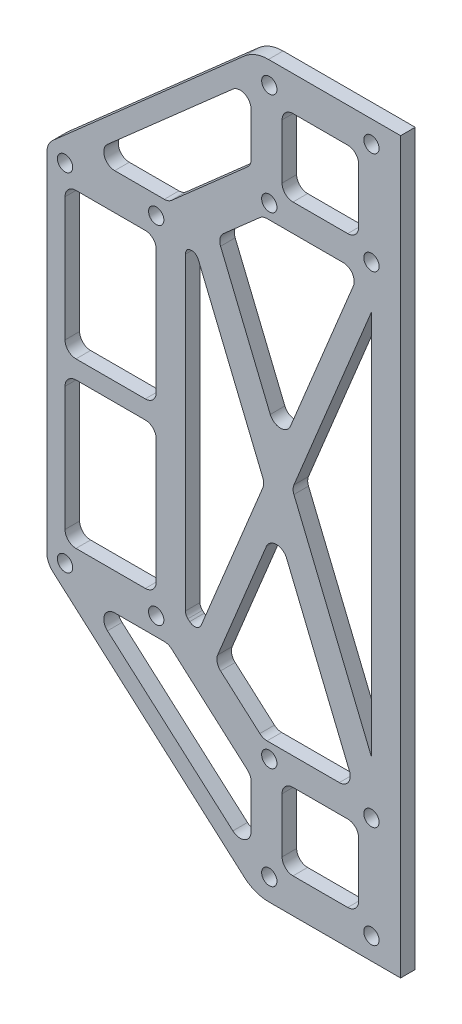
SolidWorks part; units mm, degrees
material "Thornel Mat VMA"
ref_plane "前视基准面" through (0, 0, 0) normal (0, 0, 1) x (1, 0, 0)
ref_plane "上视基准面" through (0, 0, 0) normal (0, 1, 0) x (1, 0, 0)
ref_plane "右视基准面" through (0, 0, 0) normal (1, 0, 0) x (0, 0, -1)
other "Configuration Table"
sketch "草图1" plane through (0, 0, 0) normal (0, 0, 1) x (1, 0, 0)
  line L0 (-20, 100) -> (-77, 55)
  line L1 (-20, -100) -> (20, -100)
  line L2 (-20, -100) -> (-20, 100)
  line L3 (-20, 100) -> (20, 100)
  line L4 (20, -100) -> (20, 100)
  line L5 (-20, -100) -> (20, 100) construction
  line L6 (-20, 100) -> (20, -100) construction
  line L7 (-77, 55) -> (-77, -55)
  line L8 (-77, -55) -> (-20, -100)
  line L9 (0, 0) -> (50000, 0) construction
  line L10 (0, 100) -> (0, -100) construction
  line L11 (-72, -47.5) -> (-47, -47.5) construction
  line L12 (-72, -47.5) -> (-72, 47.5) construction
  line L13 (-72, 47.5) -> (-47, 47.5) construction
  line L14 (-47, -47.5) -> (-47, 47.5) construction
  line L15 (-72, -47.5) -> (-47, 47.5) construction
  line L16 (-72, 47.5) -> (-47, -47.5) construction
  line L18 (-20, 60) -> (20, 60) construction
  line L19 (-20, 60) -> (-20, 100) construction
  line L20 (-20, 100) -> (20, 100) construction
  line L21 (20, 60) -> (20, 100) construction
  line L22 (-20, 60) -> (20, 100) construction
  line L23 (-20, 100) -> (20, 60) construction
  line L24 (-20, -60) -> (20, -60) construction
  line L25 (-20, -60) -> (-20, -100) construction
  line L26 (-20, -100) -> (20, -100) construction
  line L27 (20, -60) -> (20, -100) construction
  line L28 (-20, -60) -> (20, -100) construction
  line L29 (-20, -100) -> (20, -60) construction
  line L30 (-16, -94) -> (16, -94) construction
  line L31 (-16, -94) -> (-16, -66) construction
  line L32 (-16, -66) -> (16, -66) construction
  line L33 (16, -94) -> (16, -66) construction
  line L34 (-16, -94) -> (16, -66) construction
  line L35 (-16, -66) -> (16, -94) construction
  circle A0 centre (-72, 47.5) radius 2.1
  circle A1 centre (-47, 47.5) radius 2.1
  circle A2 centre (-72, -47.5) radius 2.1
  circle A3 centre (-47, -47.5) radius 2.1
  circle A4 centre (-16, -66) radius 2.1
  circle A6 centre (-16, -94) radius 2.1
  circle A9 centre (-16, 94) radius 2.1
  circle A12 centre (-16, 66) radius 2.1
  point P0 (0, 0)
  point P10 (-59.5, 0)
  point P21 (0, 80)
  point P22 (0, -80)
  point P26 (0, -80)
  dimension "D7" = 4.2
  dimension "D12" = 4.2
  dimension "D13" = 28
  dimension "D1" = 40
  dimension "D2" = 200
  dimension "D3" = 5
  dimension "D4" = 110
  dimension "D5" = 25
  dimension "D6" = 95
  dimension "D8" = 39.5
  dimension "D9" = 40
  dimension "D10" = 40
  dimension "D11" = 32
extrude "凸台-拉伸1" add sketch "草图1" along normal blind 4 contours L7 L8 L2 L0 A3 A2 A1 A0 | L1 L4 L3 L2 region at (-45.6551, 0, 0) region at (0.1116, 0, 0)
sketch "草图6" plane through (0, 0, 0) normal (0, 0, -1) x (-1, 0, 0)
  line L0 (77, 55) -> (77, -55) construction
  line L1 (75.3062, 51.2509) -> (20, 100)
  line L2 (20, 100) -> (77, 55)
  line L3 (77, 55) -> (77, 47.5)
  line L4 (75.3062, -51.2509) -> (20, -100)
  line L5 (20, -100) -> (77, -55)
  line L6 (77, -55) -> (77, -47.5)
  circle A0 centre (72, 47.5) radius 5
  circle A1 centre (72, -47.5) radius 5
  line M6 (20, -100) -> (77, -55)
  line M7 (77, -55) -> (77, 55)
  line M8 (77, 55) -> (20, 100)
  dimension "D1" = 73.7241
  dimension "D2" = 72.6223
  dimension "D3" = 7.5
  dimension "D4" = 73.7241
  dimension "D5" = 72.6223
  dimension "D6" = 7.5
extrude "切除-拉伸2" cut sketch "草图6" against normal blind 13 contours A0 L1 M7 M8 | A1 L4 M6 M7 region at (-58.0852, -68.1675, 0) region at (-58.0852, 68.1675, 0)
sketch "草图8" plane through (0, 0, 4) normal (0, 0, 1) x (1, 0, 0)
  line L1 (-16, 94) -> (12, 94) construction
  line L2 (-16, 94) -> (-16, 66) construction
  line L3 (-16, 66) -> (12, 66) construction
  line L4 (12, 94) -> (12, 66) construction
  line L5 (-16, -66) -> (12, -66) construction
  line L6 (-16, -66) -> (-16, -94) construction
  line L7 (-16, -94) -> (12, -94) construction
  line L8 (12, -66) -> (12, -94) construction
  circle A0 centre (12, 94) radius 2.1
  circle A1 centre (12, 66) radius 2.1
  circle A2 centre (12, -66) radius 2.1
  circle A3 centre (12, -94) radius 2.1
  dimension "D2" = 4.2
  dimension "D1" = 28
extrude "切除-拉伸3" cut sketch "草图8" against normal blind 4
sketch "草图9" plane through (0, 0, 4) normal (0, 0, 1) x (1, 0, 0)
  line L0 (-20, -100) -> (20, -100) construction
  line L1 (20, 100) -> (16, 100)
  line L2 (20, 100) -> (20, -100)
  line L3 (20, -100) -> (16, -100)
  line L4 (16, 100) -> (16, -100)
  line L5 (20, -100) -> (20, 100) construction
  circle A0 centre (12, 94) radius 2.1 construction
  dimension "D1" = 4
extrude "凸台-拉伸4" add sketch "草图9" against normal up to surface (4 mm away) up to face at (14.1, -94, 0)
fillet "圆角2" radius 10 2 edges at (-20, 100, 2) (-20, -100, 2)
sketch "草图10" plane through (0, 0, 4) normal (0, 0, 1) x (1, 0, 0)
  line L4 (-21, 92.4535) -> (-66.3275, 52.5)
  line L5 (-66.3275, 52.5) -> (-43.6427, 52.5)
  line L6 (-43.6427, 52.5) -> (-21, 72.4582)
  line L7 (-21, 72.4582) -> (-21, 92.4535)
  line L8 (-22.8343, 97.5018) -> (-75.3062, 51.2509) construction
  line L9 (-59.5, 47.5) -> (-59.5, -47.5) construction
  line L10 (-16, 66) -> (12, 66) construction
  line L11 (-16, 66) -> (-16, 94) construction
  line L12 (-16, 94) -> (12, 94) construction
  line L13 (12, 66) -> (12, 94) construction
  line L14 (-16, 66) -> (12, 94) construction
  line L15 (-16, 94) -> (12, 66) construction
  line L16 (-12.5, 69.5) -> (8.5, 69.5)
  line L17 (-12.5, 69.5) -> (-12.5, 90.5)
  line L18 (-12.5, 90.5) -> (8.5, 90.5)
  line L19 (8.5, 69.5) -> (8.5, 90.5)
  line L20 (-12.5, 69.5) -> (8.5, 90.5) construction
  line L21 (-12.5, 90.5) -> (8.5, 69.5) construction
  line L22 (-47, -47.5) -> (-72, -47.5) construction
  line L23 (-47, -47.5) -> (-47, 47.5) construction
  line L24 (-47, 47.5) -> (-72, 47.5) construction
  line L25 (-72, -47.5) -> (-72, 47.5) construction
  line L26 (-47, -47.5) -> (-72, 47.5) construction
  line L27 (-47, 47.5) -> (-72, -47.5) construction
  line L28 (-72, 0) -> (-47, 0) construction
  line L29 (-72, 2.5) -> (-47, 2.5)
  line L30 (-72, 2.5) -> (-72, 42.5)
  line L31 (-72, 42.5) -> (-47, 42.5)
  line L32 (-47, 2.5) -> (-47, 42.5)
  line L33 (-72, 2.5) -> (-47, 42.5) construction
  line L34 (-72, 42.5) -> (-47, 2.5) construction
  line L35 (-72, -42.5) -> (-47, -42.5)
  line L36 (-72, -42.5) -> (-72, -2.5)
  line L37 (-72, -2.5) -> (-47, -2.5)
  line L38 (-47, -42.5) -> (-47, -2.5)
  line L39 (-72, -42.5) -> (-47, -2.5) construction
  line L40 (-72, -2.5) -> (-47, -42.5) construction
  line L41 (-77, 47.5) -> (-77, -47.5) construction
  line L42 (-17.7417, 62) -> (-39, 43.2621)
  line L43 (-39, 43.2621) -> (-39, -43.2621)
  line L44 (-39, -43.2621) -> (-17.7417, -62)
  line L45 (-17.7417, -62) -> (12, -62)
  line L46 (12, -62) -> (12, 62)
  line L47 (12, 62) -> (-17.7417, 62)
  line L48 (0, 0) -> (50000, 0) construction
  line L50 (-39, 62) -> (12, -62) construction
  line L51 (12, 62) -> (-39, 62) construction
  line L52 (12, 62) -> (12, -62) construction
  line L53 (12, -62) -> (-39, -62) construction
  line L54 (-39, 62) -> (-39, -62) construction
  line L55 (-39, -62) -> (12, 62) construction
  line L56 (-36.5181, 45.4497) -> (7.6749, -62)
  line L57 (-30.1695, 51.0457) -> (12, -51.4841)
  line L58 (8.7562, 62) -> (-35.7245, -46.1492)
  line L59 (12, 54.113) -> (-30.9631, -50.3462)
  line L60 (-43.6427, -52.5) -> (-21, -72.4582)
  line L61 (-66.3275, -52.5) -> (-43.6427, -52.5)
  line L62 (-21, -92.4535) -> (-66.3275, -52.5)
  line L63 (-21, -72.4582) -> (-21, -92.4535)
  line L64 (-12.5, -90.5) -> (8.5, -90.5)
  line L65 (8.5, -69.5) -> (8.5, -90.5)
  line L66 (-12.5, -69.5) -> (8.5, -69.5)
  line L67 (-12.5, -69.5) -> (-12.5, -90.5)
  circle A0 centre (-47, 47.5) radius 2.1 construction
  circle A1 centre (-16, 94) radius 2.1 construction
  point P4 (-2, 80)
  point P15 (-2, 80)
  point P22 (-59.5, 0)
  point P27 (-59.5, 22.5)
  point P36 (-59.5, -22.5)
  dimension "D1" = 5
  dimension "D2" = 5
  dimension "D3" = 5
  dimension "D4" = 15
  dimension "D5" = 3.5
  dimension "D6" = 5
  dimension "D7" = 5
  dimension "D8" = 5
  dimension "D9" = 4
  dimension "D10" = 10
  dimension "D11" = 8
  dimension "D12" = 8
  dimension "D13" = 6
extrude "切除-拉伸5" cut sketch "草图10" against normal blind 13 contours L58 L47 L42 L57 | L58 L56 L42 L43 L44 | L46 L59 L57 | L56 L59 L44 L45 | L35 L38 L37 L36 | L29 L32 L31 L30 | L6 L7 L4 L5 | L16 L19 L18 L17 | L63 L60 L61 L62 | L66 L67 L64 L65 region at (-38.6235, 68.034, 4) region at (-2, 80, 4) region at (-59.5, 22.5, 4) region at (-59.5, -22.5, 4) region at (-11.6771, 43.1729, 4) region at (-31.6054, -1.0136, 4) region at (4.7615, 1.3145, 4) region at (-12.6184, -43.0183, 4) region at (-38.6235, -68.034, 4) region at (-2, -80, 4)
fillet "圆角3" radius 2 4 edges at (-35.7245, -46.1492, 2) (-39, -43.2621, 2) (-39, 43.2621, 2) (-36.5181, 45.4497, 2)
fillet "圆角4" radius 3 34 edges at (-21, -92.4535, 2) (-66.3275, -52.5, 2) (-43.6427, -52.5, 2) (-21, -72.4582, 2) (7.6749, -62, 2) (-17.7417, -62, 2) (-30.9631, -50.3462, 2) (-14.0406, -9.2015, 2) (-72, -2.5, 2) (-47, -2.5, 2) (-47, -42.5, 2) (-72, -42.5, 2) (-12.9594, 9.2015, 2) (-30.1695, 51.0457, 2) (-17.7417, 62, 2) (8.7562, 62, 2) (8.5, -69.5, 2) (8.5, -90.5, 2) (-12.5, -90.5, 2) (-12.5, -69.5, 2) (-9.7155, 1.3145, 2) (-12.5, 90.5, 2) (8.5, 90.5, 2) (8.5, 69.5, 2) (-12.5, 69.5, 2) (-66.3275, 52.5, 2) (-21, 92.4535, 2) (-21, 72.4582, 2) (-43.6427, 52.5, 2) (-72, 42.5, 2) (-47, 42.5, 2) (-47, 2.5, 2) (-72, 2.5, 2) (-17.2845, -1.3145, 2)
